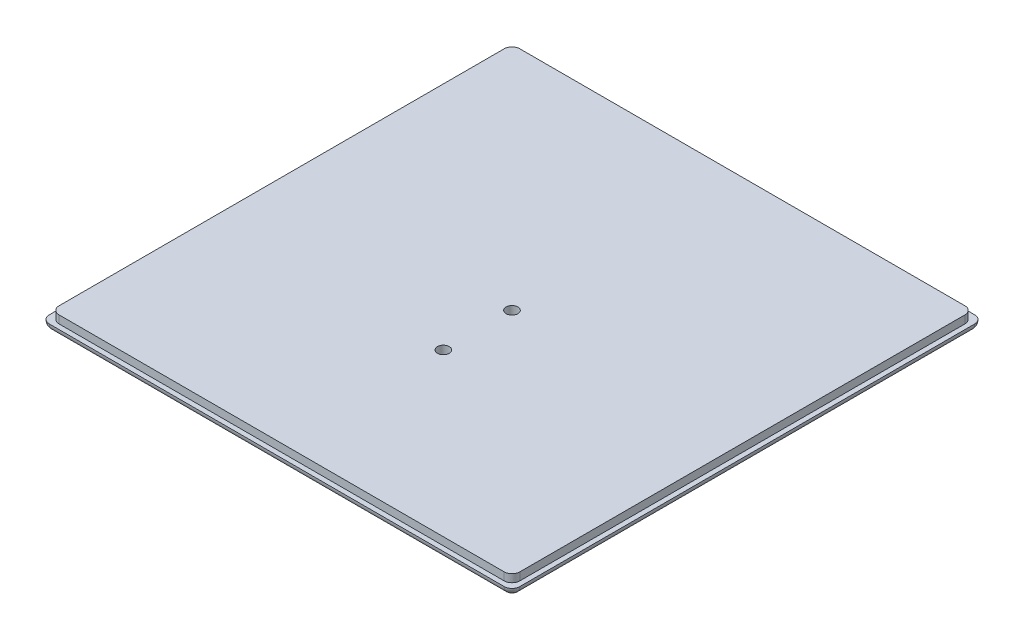
SolidWorks part; units mm, degrees
ref_plane "Front Plane" through (0, 0, 0) normal (0, 0, 1) x (1, 0, 0)
ref_plane "Top Plane" through (0, 0, 0) normal (0, 1, 0) x (1, 0, 0)
ref_plane "Right Plane" through (0, 0, 0) normal (1, 0, 0) x (0, 0, -1)
sketch "Sketch1" plane through (0, 0, 0) normal (0, 1, 0) x (1, 0, 0)
  line L1 (-60, -60) -> (60, -60)
  line L2 (-60, -60) -> (-60, 60)
  line L3 (-60, 60) -> (60, 60)
  line L4 (60, -60) -> (60, 60)
  line L5 (-60, -60) -> (60, 60) construction
  line L6 (-60, 60) -> (60, -60) construction
  point P0 (0, 0)
  dimension "D1" = 120
  dimension "D2" = 120
extrude "Boss-Extrude1" add sketch "Sketch1" along normal blind 2
sketch "Sketch2" plane through (0, 2, 0) normal (0, 1, 0) x (1, 0, 0)
  line L1 (-58.75, -58.75) -> (58.75, -58.75)
  line L2 (-58.75, -58.75) -> (-58.75, 58.75)
  line L3 (-58.75, 58.75) -> (58.75, 58.75)
  line L4 (58.75, -58.75) -> (58.75, 58.75)
  line L5 (-58.75, -58.75) -> (58.75, 58.75) construction
  line L6 (-58.75, 58.75) -> (58.75, -58.75) construction
  point P0 (0, 0)
  dimension "D1" = 117.5
  dimension "D2" = 117.5
extrude "Boss-Extrude2" add sketch "Sketch2" along normal blind 2
fillet "Fillet1" radius 2 8 edges at (-58.75, 3, -58.75) (58.75, 3, -58.75) (58.75, 3, 58.75) (-58.75, 3, 58.75) (-60, 0, 0) (0, 0, 60) (0, 0, -60) (60, 0, 0)
sketch "Sketch4" plane through (0, 0, 0) normal (0, -1, 0) x (1, 0, 0)
  circle A0 centre (0, 0) radius 1.5
  circle A1 centre (0, 17.5) radius 1.5
  dimension "D1" = 3
  dimension "D2" = 3
  dimension "D3" = 17.5
extrude "Cut-Extrude1" cut sketch "Sketch4" against normal through all
